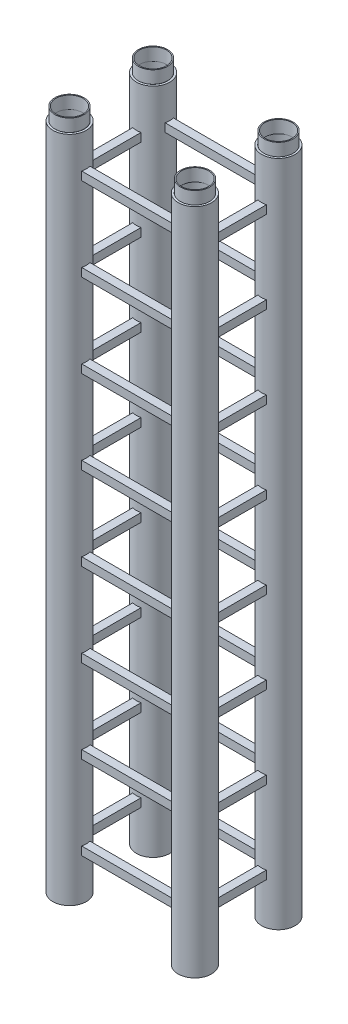
SolidWorks part; units mm, degrees
ref_plane "Front Plane" through (0, 0, 0) normal (0, 0, 1) x (1, 0, 0)
ref_plane "Top Plane" through (0, 0, 0) normal (0, 1, 0) x (1, 0, 0)
ref_plane "Right Plane" through (0, 0, 0) normal (1, 0, 0) x (0, 0, -1)
sketch "Sketch1" plane through (0, 0, 0) normal (0, 1, 0) x (1, 0, 0)
  line L1 (-750, -500) -> (750, -500) construction
  line L2 (-750, -500) -> (-750, 500) construction
  line L3 (-750, 500) -> (750, 500) construction
  line L4 (750, -500) -> (750, 500) construction
  line L5 (-750, -500) -> (750, 500) construction
  line L6 (-750, 500) -> (750, -500) construction
  circle A0 centre (-750, 500) radius 200
  circle A1 centre (750, 500) radius 200
  circle A2 centre (750, -500) radius 200
  circle A3 centre (-750, -500) radius 200
  circle A4 centre (-750, 500) radius 175
  circle A5 centre (750, 500) radius 175
  circle A6 centre (750, -500) radius 175
  circle A7 centre (-750, -500) radius 175
  point P0 (0, 0)
  dimension "D3" = 400
  dimension "D4" = 350
  dimension "D1" = 1500
  dimension "D2" = 1000
extrude "Boss-Extrude1" add sketch "Sketch1" along normal blind 8000
ref_plane "Plane1" through (750, 0, 0) normal (1, 0, 0) x (0, 0, -1)
ref_plane "Plane2" through (-750, 0, 0) normal (1, 0, 0) x (0, 0, -1)
ref_plane "Plane3" through (0, 0, 500) normal (0, 0, 1) x (1, 0, 0)
ref_plane "Plane4" through (0, 0, -500) normal (0, 0, 1) x (1, 0, 0)
sketch "Sketch2" plane through (0, 8000, 0) normal (0, 1, 0) x (1, 0, 0)
  line L0 (-1045, 500) -> (1045, 500) construction
  line L1 (0, 500) -> (0, -500) construction
  line L2 (0, 0) -> (0, -500) construction
  line L3 (-1045, -500) -> (1045, -500) construction
  line L4 (0, 0) -> (750, 0) construction
  line L5 (750, -770) -> (750, 770) construction
  line L6 (0, 0) -> (-750, 0) construction
  line L7 (-750, -770) -> (-750, 770) construction
  circle A0 centre (-751.9521, 500) radius 175
  circle A1 centre (-751.9521, 500) radius 162.5
  circle A2 centre (751.9521, 500) radius 162.5
  circle A3 centre (751.9521, 500) radius 175
  circle A4 centre (751.9521, -500) radius 175
  circle A5 centre (751.9521, -500) radius 162.5
  circle A6 centre (-751.9521, -500) radius 162.5
  circle A7 centre (-751.9521, -500) radius 175
  dimension "D1" = 350
  dimension "D2" = 325
extrude "Boss-Extrude2" add sketch "Sketch2" along normal blind 150
sketch "Sketch3" plane through (750, 0, 0) normal (1, 0, 0) x (0, 0, -1)
  line L0 (0, 500) -> (0, 0) construction
  line L1 (-365, 600) -> (365, 600)
  line L2 (-365, 600) -> (-365, 500)
  line L3 (-365, 500) -> (365, 500)
  line L4 (365, 600) -> (365, 500)
  line L5 (-700, 0) -> (-300, 0) construction
  line L6 (-365, 1585.7143) -> (-365, 1485.7143)
  line L7 (-365, 1585.7143) -> (365, 1585.7143)
  line L8 (365, 1585.7143) -> (365, 1485.7143)
  line L9 (-365, 1485.7143) -> (365, 1485.7143)
  line L10 (-365, 2571.4286) -> (-365, 2471.4286)
  line L11 (-365, 2571.4286) -> (365, 2571.4286)
  line L12 (365, 2571.4286) -> (365, 2471.4286)
  line L13 (-365, 2471.4286) -> (365, 2471.4286)
  line L14 (-365, 3557.1429) -> (-365, 3457.1429)
  line L15 (-365, 3557.1429) -> (365, 3557.1429)
  line L16 (365, 3557.1429) -> (365, 3457.1429)
  line L17 (-365, 3457.1429) -> (365, 3457.1429)
  line L18 (-365, 4542.8571) -> (-365, 4442.8571)
  line L19 (-365, 4542.8571) -> (365, 4542.8571)
  line L20 (365, 4542.8571) -> (365, 4442.8571)
  line L21 (-365, 4442.8571) -> (365, 4442.8571)
  line L22 (-365, 5528.5714) -> (-365, 5428.5714)
  line L23 (-365, 5528.5714) -> (365, 5528.5714)
  line L24 (365, 5528.5714) -> (365, 5428.5714)
  line L25 (-365, 5428.5714) -> (365, 5428.5714)
  line L26 (-365, 6514.2857) -> (-365, 6414.2857)
  line L27 (-365, 6514.2857) -> (365, 6514.2857)
  line L28 (365, 6514.2857) -> (365, 6414.2857)
  line L29 (-365, 6414.2857) -> (365, 6414.2857)
  line L30 (-365, 7500) -> (-365, 7400)
  line L31 (-365, 7500) -> (365, 7500)
  line L32 (365, 7500) -> (365, 7400)
  line L33 (-365, 7400) -> (365, 7400)
  line L67 (-300, 8000) -> (-700, 8000) construction
  dimension "D1" = 100
  dimension "D2" = 500
  dimension "D4" = 730
  dimension "D5" = 500
  dimension "D6" = 885.7143
  dimension "D3" = 8
extrude "Boss-Extrude3" add sketch "Sketch3" along normal blind 50 and the other way blind 50 from surface starting at plane "Plane1"
sketch "Sketch4" plane through (-750, 0, 0) normal (1, 0, 0) x (0, 0, -1)
  line L0 (-365, 600) -> (365, 600) construction
  line L1 (365, 600) -> (365, 500) construction
  line L2 (-365, 500) -> (365, 500) construction
  line L3 (-365, 600) -> (-365, 500) construction
  line L4 (-365, 1585.7143) -> (365, 1585.7143) construction
  line L5 (365, 1585.7143) -> (365, 1485.7143) construction
  line L6 (-365, 1485.7143) -> (365, 1485.7143) construction
  line L7 (-365, 1585.7143) -> (-365, 1485.7143) construction
  line L8 (-365, 2571.4286) -> (365, 2571.4286) construction
  line L9 (365, 2571.4286) -> (365, 2471.4286) construction
  line L10 (-365, 2471.4286) -> (365, 2471.4286) construction
  line L11 (-365, 2571.4286) -> (-365, 2471.4286) construction
  line L12 (-365, 3557.1429) -> (365, 3557.1429) construction
  line L13 (365, 3557.1429) -> (365, 3457.1429) construction
  line L14 (-365, 3457.1429) -> (365, 3457.1429) construction
  line L15 (-365, 3557.1429) -> (-365, 3457.1429) construction
  line L16 (-365, 4542.8571) -> (365, 4542.8571) construction
  line L17 (365, 4542.8571) -> (365, 4442.8571) construction
  line L18 (-365, 4442.8571) -> (365, 4442.8571) construction
  line L19 (-365, 4542.8571) -> (-365, 4442.8571) construction
  line L20 (-365, 5528.5714) -> (365, 5528.5714) construction
  line L21 (365, 5528.5714) -> (365, 5428.5714) construction
  line L22 (-365, 5428.5714) -> (365, 5428.5714) construction
  line L23 (-365, 5528.5714) -> (-365, 5428.5714) construction
  line L24 (-365, 6514.2857) -> (365, 6514.2857) construction
  line L25 (365, 6514.2857) -> (365, 6414.2857) construction
  line L26 (-365, 6414.2857) -> (365, 6414.2857) construction
  line L27 (-365, 6514.2857) -> (-365, 6414.2857) construction
  line L28 (-365, 7500) -> (365, 7500) construction
  line L29 (365, 7500) -> (365, 7400) construction
  line L30 (-365, 7400) -> (365, 7400) construction
  line L31 (-365, 7500) -> (-365, 7400) construction
  line L64 (-365, 600) -> (365, 600)
  line L65 (365, 600) -> (365, 500)
  line L66 (-365, 500) -> (365, 500)
  line L67 (-365, 600) -> (-365, 500)
  line L68 (-365, 1585.7143) -> (365, 1585.7143)
  line L69 (365, 1585.7143) -> (365, 1485.7143)
  line L70 (-365, 1485.7143) -> (365, 1485.7143)
  line L71 (-365, 1585.7143) -> (-365, 1485.7143)
  line L72 (-365, 2571.4286) -> (365, 2571.4286)
  line L73 (365, 2571.4286) -> (365, 2471.4286)
  line L74 (-365, 2471.4286) -> (365, 2471.4286)
  line L75 (-365, 2571.4286) -> (-365, 2471.4286)
  line L76 (-365, 3557.1429) -> (365, 3557.1429)
  line L77 (365, 3557.1429) -> (365, 3457.1429)
  line L78 (-365, 3457.1429) -> (365, 3457.1429)
  line L79 (-365, 3557.1429) -> (-365, 3457.1429)
  line L80 (-365, 4542.8571) -> (365, 4542.8571)
  line L81 (365, 4542.8571) -> (365, 4442.8571)
  line L82 (-365, 4442.8571) -> (365, 4442.8571)
  line L83 (-365, 4542.8571) -> (-365, 4442.8571)
  line L84 (-365, 5528.5714) -> (365, 5528.5714)
  line L85 (365, 5528.5714) -> (365, 5428.5714)
  line L86 (-365, 5428.5714) -> (365, 5428.5714)
  line L87 (-365, 5528.5714) -> (-365, 5428.5714)
  line L88 (-365, 6514.2857) -> (365, 6514.2857)
  line L89 (365, 6514.2857) -> (365, 6414.2857)
  line L90 (-365, 6414.2857) -> (365, 6414.2857)
  line L91 (-365, 6514.2857) -> (-365, 6414.2857)
  line L92 (-365, 7500) -> (365, 7500)
  line L93 (365, 7500) -> (365, 7400)
  line L94 (-365, 7400) -> (365, 7400)
  line L95 (-365, 7500) -> (-365, 7400)
extrude "Boss-Extrude4" add sketch "Sketch4" along normal blind 50 and the other way blind 50
sketch "Sketch5" plane through (0, 0, 500) normal (0, 0, 1) x (1, 0, 0)
  line L0 (0, 500) -> (0, 0) construction
  line L5 (-950, 0) -> (-550, 0) construction
  line L6 (-600, 600) -> (-600, 500)
  line L7 (-600, 600) -> (600, 600)
  line L8 (600, 600) -> (600, 500)
  line L9 (-600, 500) -> (600, 500)
  line L10 (-550, 8000) -> (-950, 8000) construction
  line L11 (-877.7682, 8000) -> (-1399.7249, 8000) construction
  line L12 (-781.6234, 0) -> (-1399.7249, 0) construction
  line L13 (-1399.7249, 0) -> (-1399.7249, 8000) construction
  line L14 (-600, 1600) -> (-600, 1500)
  line L15 (-600, 1500) -> (600, 1500)
  line L16 (600, 1600) -> (600, 1500)
  line L17 (-600, 1600) -> (600, 1600)
  line L18 (-600, 2600) -> (-600, 2500)
  line L19 (-600, 2500) -> (600, 2500)
  line L20 (600, 2600) -> (600, 2500)
  line L21 (-600, 2600) -> (600, 2600)
  line L22 (-600, 3600) -> (-600, 3500)
  line L23 (-600, 3500) -> (600, 3500)
  line L24 (600, 3600) -> (600, 3500)
  line L25 (-600, 3600) -> (600, 3600)
  line L26 (-600, 4600) -> (-600, 4500)
  line L27 (-600, 4500) -> (600, 4500)
  line L28 (600, 4600) -> (600, 4500)
  line L29 (-600, 4600) -> (600, 4600)
  line L30 (-600, 5600) -> (-600, 5500)
  line L31 (-600, 5500) -> (600, 5500)
  line L32 (600, 5600) -> (600, 5500)
  line L33 (-600, 5600) -> (600, 5600)
  line L34 (-600, 6600) -> (-600, 6500)
  line L35 (-600, 6500) -> (600, 6500)
  line L36 (600, 6600) -> (600, 6500)
  line L37 (-600, 6600) -> (600, 6600)
  line L38 (-600, 7600) -> (-600, 7500)
  line L39 (-600, 7500) -> (600, 7500)
  line L40 (600, 7600) -> (600, 7500)
  line L41 (-600, 7600) -> (600, 7600)
  point P1 (0, 500)
  dimension "D1" = 1200
  dimension "D2" = 100
  dimension "D3" = 500
  dimension "D4" = 8000
  dimension "D5" = 8
extrude "Boss-Extrude6" add sketch "Sketch5" along normal blind 50 and the other way blind 50
sketch "Sketch6" plane through (0, 0, -500) normal (0, 0, 1) x (1, 0, 0)
  line L0 (-556.3508, 500) -> (556.3508, 500) construction
  line L1 (556.3508, 500) -> (556.3508, 600) construction
  line L2 (556.3508, 600) -> (-556.3508, 600) construction
  line L3 (-556.3508, 600) -> (-556.3508, 500) construction
  line L4 (-556.3508, 1600) -> (-556.3508, 1500) construction
  line L5 (-556.3508, 1500) -> (556.3508, 1500) construction
  line L6 (556.3508, 1500) -> (556.3508, 1600) construction
  line L7 (556.3508, 1600) -> (-556.3508, 1600) construction
  line L8 (-556.3508, 2500) -> (556.3508, 2500) construction
  line L9 (556.3508, 2500) -> (556.3508, 2600) construction
  line L10 (556.3508, 2600) -> (-556.3508, 2600) construction
  line L11 (-556.3508, 2600) -> (-556.3508, 2500) construction
  line L12 (-556.3508, 3500) -> (556.3508, 3500) construction
  line L13 (556.3508, 3500) -> (556.3508, 3600) construction
  line L14 (556.3508, 3600) -> (-556.3508, 3600) construction
  line L15 (-556.3508, 3600) -> (-556.3508, 3500) construction
  line L16 (-556.3508, 4500) -> (556.3508, 4500) construction
  line L17 (556.3508, 4500) -> (556.3508, 4600) construction
  line L18 (556.3508, 4600) -> (-556.3508, 4600) construction
  line L19 (-556.3508, 4600) -> (-556.3508, 4500) construction
  line L20 (-556.3508, 5500) -> (556.3508, 5500) construction
  line L21 (556.3508, 5500) -> (556.3508, 5600) construction
  line L22 (556.3508, 5600) -> (-556.3508, 5600) construction
  line L23 (-556.3508, 5600) -> (-556.3508, 5500) construction
  line L24 (-556.3508, 6500) -> (556.3508, 6500) construction
  line L25 (556.3508, 6500) -> (556.3508, 6600) construction
  line L26 (556.3508, 6600) -> (-556.3508, 6600) construction
  line L27 (-556.3508, 6600) -> (-556.3508, 6500) construction
  line L28 (-556.3508, 7500) -> (556.3508, 7500) construction
  line L29 (556.3508, 7500) -> (556.3508, 7600) construction
  line L30 (556.3508, 7600) -> (-556.3508, 7600) construction
  line L31 (-556.3508, 7600) -> (-556.3508, 7500) construction
  line L32 (-556.3508, 500) -> (556.3508, 500)
  line L33 (556.3508, 500) -> (556.3508, 600)
  line L34 (556.3508, 600) -> (-556.3508, 600)
  line L35 (-556.3508, 600) -> (-556.3508, 500)
  line L36 (-556.3508, 1600) -> (-556.3508, 1500)
  line L37 (-556.3508, 1500) -> (556.3508, 1500)
  line L38 (556.3508, 1500) -> (556.3508, 1600)
  line L39 (556.3508, 1600) -> (-556.3508, 1600)
  line L40 (-556.3508, 2500) -> (556.3508, 2500)
  line L41 (556.3508, 2500) -> (556.3508, 2600)
  line L42 (556.3508, 2600) -> (-556.3508, 2600)
  line L43 (-556.3508, 2600) -> (-556.3508, 2500)
  line L44 (-556.3508, 3500) -> (556.3508, 3500)
  line L45 (556.3508, 3500) -> (556.3508, 3600)
  line L46 (556.3508, 3600) -> (-556.3508, 3600)
  line L47 (-556.3508, 3600) -> (-556.3508, 3500)
  line L48 (-556.3508, 4500) -> (556.3508, 4500)
  line L49 (556.3508, 4500) -> (556.3508, 4600)
  line L50 (556.3508, 4600) -> (-556.3508, 4600)
  line L51 (-556.3508, 4600) -> (-556.3508, 4500)
  line L52 (-556.3508, 5500) -> (556.3508, 5500)
  line L53 (556.3508, 5500) -> (556.3508, 5600)
  line L54 (556.3508, 5600) -> (-556.3508, 5600)
  line L55 (-556.3508, 5600) -> (-556.3508, 5500)
  line L56 (-556.3508, 6500) -> (556.3508, 6500)
  line L57 (556.3508, 6500) -> (556.3508, 6600)
  line L58 (556.3508, 6600) -> (-556.3508, 6600)
  line L59 (-556.3508, 6600) -> (-556.3508, 6500)
  line L60 (-556.3508, 7500) -> (556.3508, 7500)
  line L61 (556.3508, 7500) -> (556.3508, 7600)
  line L62 (556.3508, 7600) -> (-556.3508, 7600)
  line L63 (-556.3508, 7600) -> (-556.3508, 7500)
extrude "Boss-Extrude7" add sketch "Sketch6" along normal blind 50 and the other way blind 50
